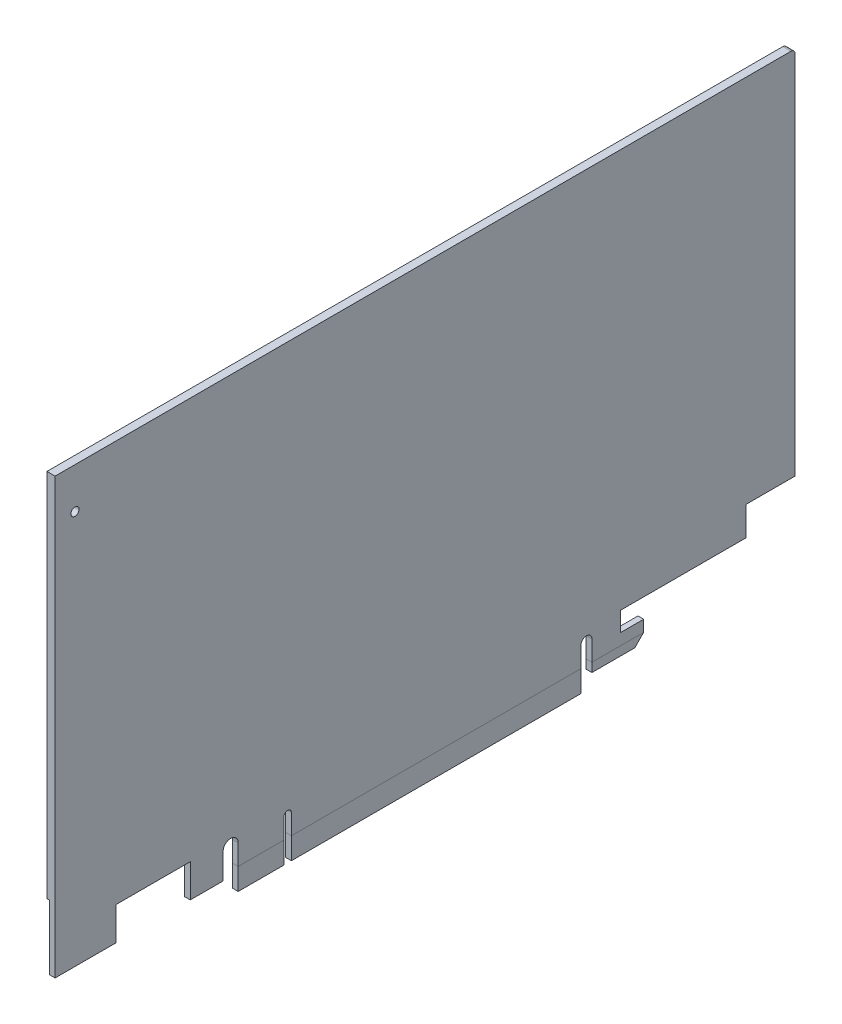
SolidWorks part; units mm, degrees
ref_plane "前视基准面" through (0, 0, 0) normal (0, 0, 1) x (1, 0, 0)
ref_plane "上视基准面" through (0, 0, 0) normal (0, 1, 0) x (1, 0, 0)
ref_plane "右视基准面" through (0, 0, 0) normal (1, 0, 0) x (0, 0, -1)
sketch "草图1" plane through (0, 0, 0) normal (1, 0, 0) x (0, 0, -1)
  line L0 (-102.4761, -30.4741) -> (-102.4761, -46.3841)
  line L7 (67.5239, -30.4741) -> (67.5239, -37.5941)
  line L8 (67.5239, -37.5941) -> (36.5939, -37.5941)
  line L9 (36.5939, -37.5941) -> (36.5939, -42.3441)
  line L10 (36.5939, -42.3441) -> (42.3039, -42.3441)
  line L11 (42.3039, -42.3441) -> (42.3039, -45.1441)
  line L14 (29.5639, -45.1441) -> (29.5639, -40.1941)
  line L15 (26.8639, -40.1941) -> (26.8639, -45.1441)
  line L17 (-44.3461, -45.1441) -> (-44.3461, -40.1941)
  line L18 (-46.1661, -40.1941) -> (-46.1661, -45.1441)
  line L20 (-57.4461, -45.1441) -> (-57.4461, -40.0841)
  line L21 (-61.1461, -40.0841) -> (-61.1461, -46.3841)
  line L22 (-61.1461, -46.3841) -> (-69.2261, -46.3841)
  line L23 (-69.2261, -46.3841) -> (-69.2261, -38.2341)
  line L24 (-69.2261, -38.2341) -> (-87.4761, -38.2341)
  line L25 (-87.4761, -38.2341) -> (-87.4761, -46.3841)
  line L26 (-87.4761, -46.3841) -> (-102.4761, -46.3841)
  line L27 (42.3039, -45.1441) -> (29.5639, -45.1441)
  line L28 (26.8639, -45.1441) -> (-44.3461, -45.1441)
  line L29 (-46.1661, -45.1441) -> (-57.4461, -45.1441)
  line L31 (26.8639, -40.1941) -> (-44.3461, -40.1941) construction
  line L32 (-102.4761, -30.4741) -> (67.5239, -30.4741)
  arc A0 (29.5639, -40.1941) -> (26.8639, -40.1941) centre (28.2139, -40.1941) ccw
  arc A1 (-44.3461, -40.1941) -> (-46.1661, -40.1941) centre (-45.2561, -40.1941) ccw
  arc A2 (-57.4461, -40.0841) -> (-61.1461, -40.0841) centre (-59.2961, -40.0841) ccw
  dimension "D5" = 170
  dimension "D9" = 30.93
  dimension "D11" = 25.22
  dimension "D12" = 4.75
  dimension "D16" = 2.7
  dimension "D18" = 12.74
  dimension "D19" = 84.31
  dimension "D23" = 15
  dimension "D24" = 18.25
  dimension "D25" = 8.08
  dimension "D26" = 8.15
extrude "凸台-拉伸1" add sketch "草图1" along normal blind 1.4
sketch "草图3" plane through (1.4, 0, 0) normal (1, 0, 0) x (0, 0, -1)
  line L1 (-44.3461, -45.1441) -> (26.8639, -45.1441)
  line L2 (-44.3461, -45.1441) -> (-44.3461, -50.4741)
  line L3 (-44.3461, -50.4741) -> (26.8639, -50.4741)
  line L4 (26.8639, -45.1441) -> (26.8639, -50.4741)
  line L6 (29.5639, -45.1441) -> (42.3039, -45.1441)
  line L7 (29.5639, -45.1441) -> (29.5639, -47.3441)
  line L8 (29.5639, -47.3441) -> (42.3039, -47.3441)
  line L9 (42.3039, -45.1441) -> (42.3039, -47.3441)
  line L10 (-57.4461, -45.1441) -> (-46.1661, -45.1441)
  line L11 (-57.4461, -45.1441) -> (-57.4461, -50.4741)
  line L12 (-57.4461, -50.4741) -> (-46.1661, -50.4741)
  line L13 (-46.1661, -45.1441) -> (-46.1661, -50.4741)
  dimension "D1" = 5.33
extrude "凸台-拉伸2" add sketch "草图3" against normal blind 1.4 separate body
chamfer "倒角1" distance 2.2 angle 45 1 edges at (0.7, -47.3441, -42.3039)
sketch "草图5" plane through (1.4, 0, 0) normal (1, 0, 0) x (0, 0, -1)
  line L0 (-44.3461, -50.4741) -> (26.8639, -50.4741) construction
  line L1 (-102.4761, -30.4741) -> (79.5239, -30.4741)
  line L2 (-102.4761, -30.4741) -> (-102.4761, 60.5259)
  line L3 (-102.4761, 60.5259) -> (79.5239, 60.5259)
  line L4 (79.5239, -30.4741) -> (79.5239, 60.5259)
  dimension "D1" = 111
extrude "凸台-拉伸4" add sketch "草图5" against normal blind 2
sketch "草图6" plane through (1.4, 0, 0) normal (1, 0, 0) x (0, 0, -1)
  line L0 (-102.4761, 60.5259) -> (-102.4761, -46.3841) construction
  line L1 (-102.4761, -46.3841) -> (-87.4761, -46.3841) construction
  circle A0 centre (-97.5861, 50.5159) radius 1
  dimension "D1" = 4.89
  dimension "D2" = 96.9
extrude "挡板螺孔" cut sketch "草图6" against normal blind 2
fillet "圆角1" radius 1 1 edges at (0.4, 60.5259, -79.5239)
